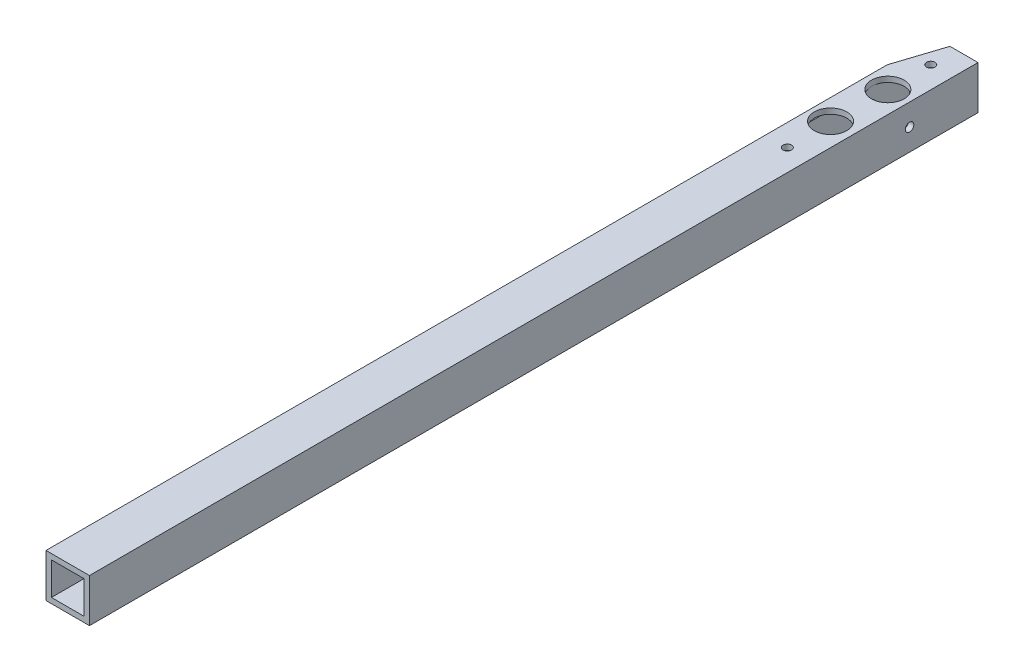
SolidWorks part; units mm, degrees
ref_plane "Front Plane" through (0, 0, 0) normal (0, 0, 1) x (1, 0, 0)
ref_plane "Top Plane" through (0, 0, 0) normal (0, 1, 0) x (1, 0, 0)
ref_plane "Right Plane" through (0, 0, 0) normal (1, 0, 0) x (0, 0, -1)
sketch "Sketch1" plane through (0, 0, 0) normal (0, 0, 1) x (1, 0, 0)
  line L0 (-9.525, 9.525) -> (9.525, 9.525)
  line L2 (-12.7, 12.7) -> (12.7, 12.7)
  line L3 (-12.7, 12.7) -> (-12.7, -12.7)
  line L4 (-12.7, -12.7) -> (12.7, -12.7)
  line L5 (12.7, 12.7) -> (12.7, -12.7)
  line L10 (9.525, 9.525) -> (9.525, -9.525)
  line L11 (-9.525, -9.525) -> (9.525, -9.525)
  line L12 (-9.525, 9.525) -> (-9.525, -9.525)
  point P12 (0, 12.7)
  point P14 (12.7, 0)
  dimension "Wall Thickness" = 3.175
  dimension "Outside Width" = 25.4
  dimension "Outside Height" = 25.4
  dimension "Inside Height" = 19.05
  dimension "Inside Width" = 19.05
sketch "Sketch2" plane through (0, 0, 0) normal (1, 0, 0) x (0, 0, -1)
  line L0 (266.7, 0) -> (-266.7, 0)
  point P4 (0, 0)
  point P7 (-266.7, 0)
  point P10 (266.7, 0)
  dimension "Length" = 533.4
sketch "Sketch3" plane through (0, 0, 0) normal (0, 0, 1) x (1, 0, 0)
  line L21 (12.7, 12.7) -> (-12.7, 12.7)
  line L22 (12.7, -12.7) -> (12.7, 12.7)
  line L23 (-12.7, -12.7) -> (12.7, -12.7)
  line L24 (-12.7, 12.7) -> (-12.7, -12.7)
  line L25 (12.7, 12.7) -> (-12.7, 12.7)
  line L26 (12.7, -12.7) -> (12.7, 12.7)
  line L27 (-12.7, -12.7) -> (12.7, -12.7)
  line L28 (-12.7, 12.7) -> (-12.7, -12.7)
  line L29 (9.525, 9.525) -> (-9.525, 9.525)
  line L30 (9.525, -9.525) -> (9.525, 9.525)
  line L31 (-9.525, -9.525) -> (9.525, -9.525)
  line L32 (-9.525, 9.525) -> (-9.525, -9.525)
  line L33 (9.525, 9.525) -> (-9.525, 9.525)
  line L34 (9.525, -9.525) -> (9.525, 9.525)
  line L35 (-9.525, -9.525) -> (9.525, -9.525)
  line L36 (-9.525, 9.525) -> (-9.525, -9.525)
  dimension "D1" = 0
  dimension "D2" = 0
extrude "Boss-Extrude1" add sketch "Sketch3" along normal up to vertex (266.7 mm away) and the other way up to vertex (266.7 mm away) up to point (0, 0, 266.7) other way up to point (0, 0, -266.7)
sketch "Drawing Reference" plane through (0, 0, 0) normal (1, 0, 0) x (0, 0, -1)
  line L0 (-266.7, 0) -> (266.7, 0) construction
  line L1 (0, -12.7) -> (0, 12.7) construction
  line L2 (-266.7, -12.7) -> (266.7, -12.7) construction
  line L5 (-266.7, 12.7) -> (266.7, 12.7) construction
  point P7 (-248.412, 0)
  point P8 (248.412, 0)
  dimension "D1" = 18.288
sketch "Sketch4" plane through (0, 12.7, 0) normal (0, 1, 0) x (1, 0, 0)
  line L1 (0, 266.7) -> (0, 212.725) construction
  line L7 (-12.7, 225.0135) -> (-12.7, 266.7)
  line L8 (-188.9197, -317.3351) -> (4.6184, 278.3139) construction
  line L10 (-12.7, -266.7) -> (-12.7, 266.7) construction
  line L11 (-12.7, 266.7) -> (12.7, 266.7)
  line L12 (12.7, 266.7) -> (12.7, 252.73)
  line L13 (12.7, -266.7) -> (12.7, 266.7) construction
  line L14 (12.7, 252.73) -> (-3.6943, 252.73)
  line L15 (-3.6943, 252.73) -> (-12.7, 225.0135)
  circle A0 centre (0, 212.725) radius 9.525
  dimension "D1" = 13.97
extrude "Cut-Extrude1" cut sketch "Sketch4" against normal blind 25.4
sketch "Sketch5" plane through (0, 12.7, 0) normal (0, -1, 0) x (1, 0, 0)
  circle A0 centre (-0.6605, -179.8709) radius 9.525
extrude "Cut-Extrude2" cut sketch "Sketch5" along normal blind 3.175
sketch "Sketch6" plane through (12.7, 0, 0) normal (1, 0, 0) x (0, 0, -1)
  line L0 (252.73, 0) -> (212.725, 0) construction
  line L1 (252.73, -12.7) -> (252.73, 12.7) construction
hole_wizard "#10 Clearance Hole1" positions "Sketch7" profile "Sketch8" hole size "#10" standard "ANSI Inch" end condition through all
sketch "Sketch7" plane through (12.7, 0, 0) normal (1, 0, 0) x (0, 0, -1)
  point P0 (212.725, 0)
sketch "Sketch8" plane through (12.7, 0, -212.725) normal (0, 1, 0) x (0, 0, -1)
  line L0 (0, 0) -> (0, 25.4)
  line L1 (0, 25.4) -> (2.4892, 25.4)
  line L2 (2.4892, 25.4) -> (2.4892, 0)
  line L5 (2.4892, 0) -> (0, 0)
  line L11 (0, -6.35) -> (0, 107.95) construction
  dimension "Thru Hole Dia." = 4.9784
  dimension "Thru Hole Depth" = 25.4
hole_wizard "#10 Clearance Hole2" positions "Sketch9" profile "Sketch10" hole size "#10" standard "ANSI Inch" end condition through all
sketch "Sketch9" plane through (0, -12.7, 0) normal (0, -1, 0) x (-1, 0, 0)
  point P0 (0, 153.96)
  point P3 (0, 237.8065)
sketch "Sketch10" plane through (0, -12.7, -153.96) normal (1, 0, 0) x (0, 0, -1)
  line L0 (0, 0) -> (0, 25.4)
  line L1 (0, 25.4) -> (2.4892, 25.4)
  line L2 (2.4892, 25.4) -> (2.4892, 0)
  line L5 (2.4892, 0) -> (0, 0)
  line L11 (0, -6.35) -> (0, 107.95) construction
  dimension "Thru Hole Dia." = 4.9784
  dimension "Thru Hole Depth" = 25.4
equation "\"D1@Drawing Reference\"=\"Outside Width@Sketch1\" * 0.72"
